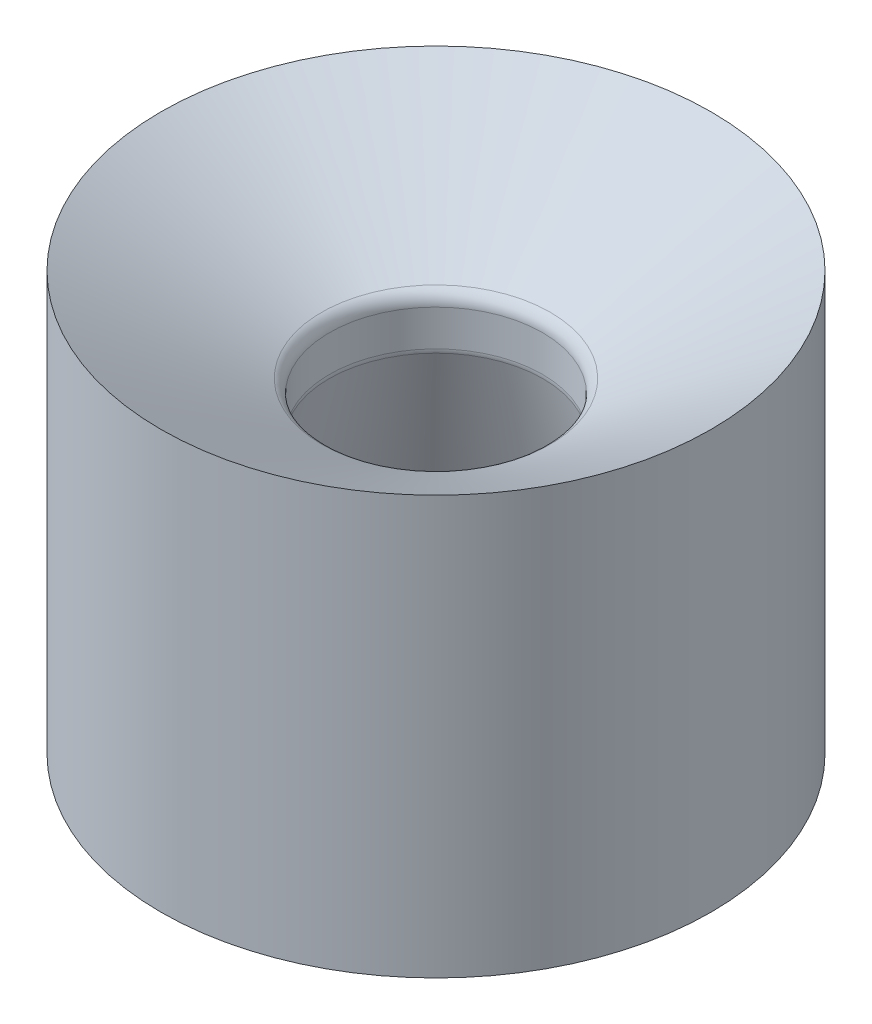
SolidWorks part; units mm, degrees
material "C (Graphite)"
ref_plane "Front Plane" through (0, 0, 0) normal (0, 0, 1) x (1, 0, 0)
ref_plane "Top Plane" through (0, 0, 0) normal (0, 1, 0) x (1, 0, 0)
ref_plane "Right Plane" through (0, 0, 0) normal (1, 0, 0) x (0, 0, -1)
sketch "Sketch1" plane through (0, 0, 0) normal (0, 1, 0) x (1, 0, 0)
  circle A0 centre (0, 0) radius 44.2849
  dimension "D1" = 88.5698
extrude "Boss-Extrude1" add sketch "Sketch1" along normal blind 86.106
sketch "Sketch2" plane through (0, 0, 0) normal (0, 0, 1) x (1, 0, 0)
  line L0 (17.145, 70.358) -> (17.145, 62.738)
  line L2 (44.2849, 86.106) -> (-44.2849, 86.106) construction
  line L3 (17.145, 62.738) -> (33.9556, 0)
  line L4 (-44.2849, 0) -> (44.2849, 0) construction
  line L5 (33.9556, 0) -> (0, 0)
  line L6 (0, 0) -> (0, 86.106)
  line L9 (17.145, 70.358) -> (44.2849, 86.106)
  line L10 (44.2849, 86.106) -> (0, 86.106)
  dimension "D1" = 17.145
  dimension "D2" = 0
  dimension "D3" = 15
  dimension "D4" = 7.62
  dimension "D5" = 70.358
ref_axis "Axis1" through (0, 86.106, 0) along (0, -1, 0)
revolve "Cut-Revolve1" cut sketch "Sketch2" angle 360 about axis through (0, 86.106, 0) along (0, -1, 0)
fillet "Fillet1" radius 2.54 2 edges at (0, 62.738, 17.145) (0, 70.358, 17.145)
other "Move Face1" flip direction yes face at (0, 0, 33.9556) offset 18.796 parameters "D1"=18.796
